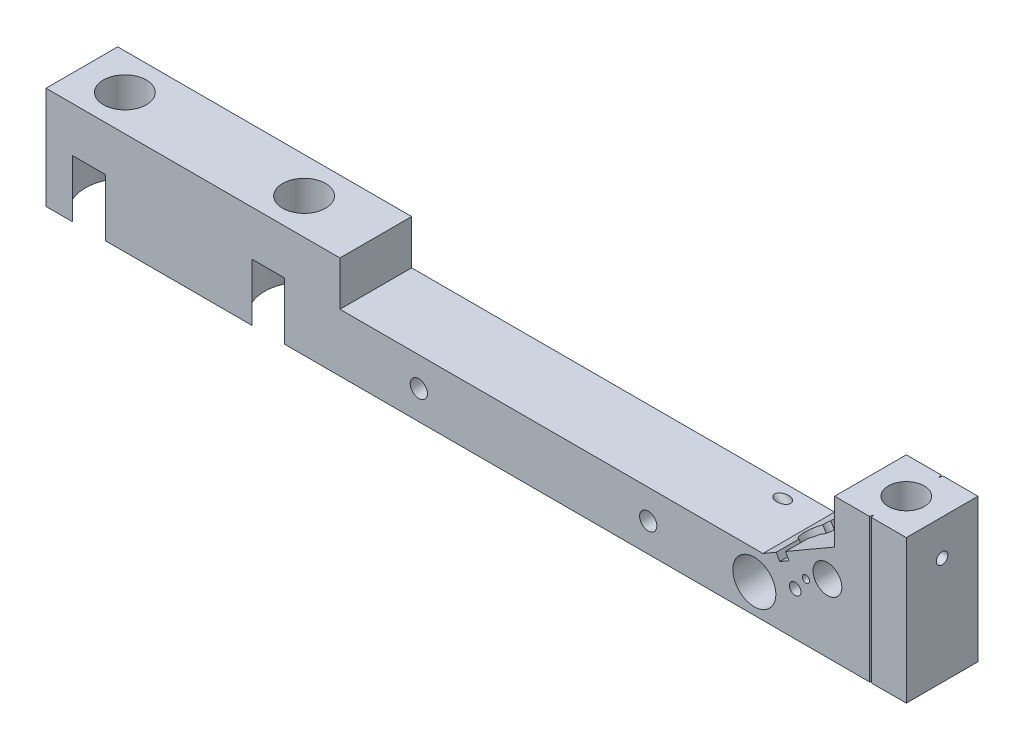
SolidWorks part; units mm, degrees
ref_plane "Front Plane" through (0, 0, 0) normal (0, 0, 1) x (1, 0, 0)
ref_plane "Top Plane" through (0, 0, 0) normal (0, 1, 0) x (1, 0, 0)
ref_plane "Right Plane" through (0, 0, 0) normal (1, 0, 0) x (0, 0, -1)
sketch "Sketch1" plane through (0, 0, 0) normal (0, 1, 0) x (1, 0, 0)
  line L1 (-13.6389, 9.0278) -> (6.3611, 9.0278)
  line L2 (-13.6389, 9.0278) -> (-13.6389, -0.9722)
  line L3 (-13.6389, -0.9722) -> (6.3611, -0.9722)
  line L4 (6.3611, 9.0278) -> (6.3611, -0.9722)
  dimension "D1" = 20
  dimension "D2" = 10
extrude "Boss-Extrude1" add sketch "Sketch1" along normal blind 20
sketch "Sketch2" plane through (0, 20, 0) normal (0, 1, 0) x (1, 0, 0)
  line L0 (-13.6389, 4.0278) -> (6.3611, 4.0278) construction
  line L1 (-13.6389, 9.0278) -> (-13.6389, -0.9722) construction
  line L2 (6.3611, -0.9722) -> (6.3611, 9.0278) construction
  line L3 (1.4951, -0.9722) -> (1.3611, -0.4722)
  line L4 (-13.6389, -0.9722) -> (6.3611, -0.9722) construction
  line L5 (1.3611, -0.4722) -> (1.2271, -0.9722)
  line L6 (1.4951, -0.9722) -> (1.2271, -0.9722)
  line L7 (1.3611, 8.5278) -> (1.2271, 9.0278)
  line L8 (1.4951, 9.0278) -> (1.3611, 8.5278)
  line L9 (1.4951, 9.0278) -> (1.2271, 9.0278)
  circle A0 centre (1.3611, 4.0278) radius 2.5
  dimension "D1" = 5
  dimension "D2" = 5
  dimension "D3" = 30
  dimension "D4" = 0.5
extrude "Cut-Extrude1" cut sketch "Sketch2" against normal through all
sketch "Sketch3" plane through (0, 0, 0.9722) normal (0, 0, 1) x (1, 0, 0)
  line L0 (-13.6389, 20) -> (-3.6389, 20)
  line L1 (-13.6389, 20) -> (1.2271, 20) construction
  line L2 (-3.6389, 13.8564) -> (-10.4894, 9.9013)
  line L3 (-13.6389, 20) -> (-13.6389, 0) construction
  line L4 (-13.6389, 8.0829) -> (-13.6389, 20)
  line L5 (-3.6389, 13.8564) -> (-3.6389, 20)
  line L6 (-13.6389, 0) -> (1.2271, 0) construction
  line L7 (-11.1389, 9.5263) -> (-5.6389, 0) construction
  line L8 (6.3611, 20) -> (6.3611, 0) construction
  line L10 (-10.4894, 9.9013) -> (-9.9894, 9.0353)
  line L11 (-11.7884, 9.1513) -> (-11.2884, 8.2853)
  line L12 (-9.9894, 9.0353) -> (-11.2884, 8.2853)
  line L13 (-11.7884, 9.1513) -> (-13.6389, 8.0829)
  point P1 (-10.6389, 8.6603)
  point P17 (-8.3889, 4.7631)
  dimension "D1" = 30
  dimension "D2" = 11
  dimension "D3" = 12
  dimension "D4" = 10
  dimension "D5" = 1.5
  dimension "D6" = 1
extrude "Cut-Extrude2" cut sketch "Sketch3" against normal through all
sketch "Sketch5" plane through (-6.9097, 11.968, 0) normal (-0.5, 0.866, 0) x (0.866, 0.5, 0)
  line L0 (-4.1334, 9.0278) -> (-4.1334, -0.9722) construction
  line L1 (-4.1334, 4.0278) -> (-5.6334, 4.0278) construction
  line L2 (-5.6334, 9.0278) -> (-5.6334, -0.9722) construction
  arc A0 (-5.85, 5.7214) -> (-3.1898, 3.0612) centre (-4.8834, 4.0278) ccw
  arc A1 (-3.9169, 5.7214) -> (-5.85, 5.7214) centre (-4.8834, 5.9778) ccw
  arc A2 (-3.1898, 3.0612) -> (-3.1898, 4.9943) centre (-2.9334, 4.0278) ccw
  arc A3 (-3.1898, 4.9943) -> (-3.9169, 5.7214) centre (-4.8834, 4.0278) ccw
  point P5 (-4.1334, 4.0278)
  dimension "D1" = 3.9
  dimension "D2" = 2
  dimension "D3" = 2
extrude "Cut-Extrude5" cut sketch "Sketch5" against normal through all
sketch "Sketch6" plane through (6.3611, 0, 0) normal (1, 0, 0) x (0, 0, -1)
  line L1 (-0.9722, 20) -> (9.0278, 20) construction
  point P0 (4.0278, 15)
  point P8 (4.0278, 20)
  dimension "D1" = 5
hole_wizard "M2x0.4 Tapped Hole1" positions "Sketch7" profile "Sketch8" tap size "M2x0.4" standard "BSI"
sketch "Sketch7" plane through (6.3611, 0, 0) normal (1, 0, 0) x (0, 0, -1)
  point P0 (4.0278, 15)
sketch "Sketch8" plane through (6.3611, 15, -4.0278) normal (0, 1, 0) x (0, 0, -1)
  line L0 (0, 0) -> (0, 6.4807)
  line L1 (0, 6.4807) -> (0.8, 6)
  line L2 (0.8, 6) -> (0.8, 0)
  line L5 (0.8, 0) -> (0, 0)
  line L10 (0, 6.4807) -> (-0.8, 6) construction
  line L11 (0, -6.35) -> (0, 107.95) construction
  dimension "Tap Drill Dia." = 1.6
  dimension "Tap Drill Depth" = 6
  dimension "Drill Angle" = 118
cosmetic thread "Hole Thread1" parameters "D1"=4, "D2"=2
hole_wizard "M2x0.4 Tapped Hole2" positions "Sketch9" profile "Sketch10" tap size "M2x0.4" standard "BSI"
sketch "Sketch9" plane through (0, 0, 0.9722) normal (0, 0, 1) x (1, 0, 0)
  line L0 (-11.2884, 8.2853) -> (-9.9894, 9.0353) construction
  line L1 (-9.1389, 6.0622) -> (-10.6389, 8.6603) construction
  point P0 (-9.1389, 6.0622)
  dimension "D1" = 3
sketch "Sketch10" plane through (-9.1389, 6.0622, 0.9722) normal (1, 0, 0) x (0, -1, 0)
  line L0 (0, 0) -> (0, 6.4807)
  line L1 (0, 6.4807) -> (0.8, 6)
  line L2 (0.8, 6) -> (0.8, 0)
  line L5 (0.8, 0) -> (0, 0)
  line L10 (0, 6.4807) -> (-0.8, 6) construction
  line L11 (0, -6.35) -> (0, 107.95) construction
  dimension "Tap Drill Dia." = 1.6
  dimension "Tap Drill Depth" = 6
  dimension "Drill Angle" = 118
cosmetic thread "Hole Thread2" parameters "D1"=4, "D2"=2
sketch "Sketch14" plane through (-13.6389, 0, 0) normal (-1, 0, 0) x (0, 0, 1)
  line L4 (0.9722, 0) -> (0.9722, 8.0829)
  line L5 (0.9722, 8.0829) -> (-9.0278, 8.0829)
  line L6 (-9.0278, 8.0829) -> (-9.0278, 0)
  line L7 (-9.0278, 0) -> (0.9722, 0)
  line L8 (0.9722, 0) -> (0.9722, 8.0829)
  line L9 (0.9722, 8.0829) -> (-9.0278, 8.0829)
  line L10 (-9.0278, 8.0829) -> (-9.0278, 0)
  line L11 (-9.0278, 0) -> (0.9722, 0)
  dimension "D1" = 0
extrude "Boss-Extrude3" add sketch "Sketch14" along normal blind 100
sketch "Sketch15" plane through (0, 8.0829, 0) normal (0, 1, 0) x (1, 0, 0)
  line L1 (-113.6389, -0.9722) -> (-113.6389, 9.0278) construction
  circle A2 centre (-107.6389, 4.0278) radius 3
  circle A3 centre (-82.6389, 4.0278) radius 3
  point P8 (-113.6389, 4.0278)
  dimension "D1" = 6
  dimension "D2" = 6
  dimension "D4" = 6
  dimension "D3" = 25
extrude "Cut-Extrude7" cut sketch "Sketch15" against normal up to next
sketch "Sketch16" plane through (0, 0, 0.9722) normal (0, 0, 1) x (1, 0, 0)
  line L0 (-113.6389, 0) -> (1.2271, 0) construction
  line L3 (-13.6389, 0) -> (-13.6389, 8.0829) construction
  circle A0 centre (-61.6389, 4) radius 1
  circle A1 centre (-29.6389, 4) radius 1
  dimension "D1" = 2
  dimension "D2" = 2
  dimension "D5" = 16
  dimension "D4" = 32
  dimension "D3" = 4
sketch "Sketch18" plane through (0, 0, 0.9722) normal (0, 0, 1) x (1, 0, 0)
  line L0 (-113.6389, 0) -> (1.2271, 0) construction
  line L1 (-13.6389, 0) -> (-13.6389, 8.0829) construction
  circle A0 centre (-7.6389, 8) radius 0.5
  dimension "D1" = 1
  dimension "D2" = 8
  dimension "D3" = 6
extrude "Cut-Extrude9" cut sketch "Sketch18" against normal blind 3
sketch "Sketch23" plane through (0, 0, 0) normal (0, -1, 0) x (1, 0, 0)
  circle A0 centre (-107.6389, -4.0278) radius 5.5
  circle A1 centre (-82.6389, -4.0278) radius 5.5
  dimension "D1" = 11
  dimension "D2" = 11
extrude "Cut-Extrude10" cut sketch "Sketch23" against normal blind 8
sketch "Sketch24" plane through (0, 8.0829, 0) normal (0, 1, 0) x (1, 0, 0)
  line L0 (-113.6389, -0.9722) -> (-13.6389, -0.9722) construction
  line L1 (-72.6389, -0.9722) -> (-113.6389, -0.9722)
  line L2 (-72.6389, -0.9722) -> (-72.6389, 9.0278)
  line L3 (-72.6389, 9.0278) -> (-113.6389, 9.0278)
  line L4 (-113.6389, -0.9722) -> (-113.6389, 9.0278)
  circle A0 centre (-82.6389, 4.0278) radius 3 construction
  circle A1 centre (-107.6389, 4.0278) radius 3
  circle A2 centre (-82.6389, 4.0278) radius 3
  point P9 (-72.6389, 4.0278)
  dimension "D1" = 10
extrude "Boss-Extrude4" add sketch "Sketch24" along normal blind 6.2
sketch "Sketch27" plane through (0, 0, -9.0278) normal (0, 0, -1) x (-1, 0, 0)
  line L0 (-6.3611, 20) -> (-6.3611, 0) construction
  line L1 (-1.2271, 0) -> (80.3476, 0) construction
  circle A0 centre (4.6389, 9.5) radius 2
  dimension "D1" = 4
  dimension "D2" = 11
  dimension "D3" = 9.5
extrude "Cut-Extrude11" cut sketch "Sketch27" against normal through all
ref_axis "Axis1" through (-4.6389, 9.5, 0.9722) along (0, 0, -1)
ref_plane "Plane1" through (0.6345, 0.3663, 0) normal (0.866, 0.5, 0) x (0, 0, -1)
sketch "Sketch28" plane through (-6.9097, 11.968, 0) normal (-0.5, 0.866, 0) x (0.866, 0.5, 0)
  line L0 (3.7768, 4.0278) -> (-99.5675, 4.0278) construction
  line L1 (3.7768, 9.0278) -> (3.7768, -0.9722) construction
  line L2 (0.7326, -4.461) -> (0.7326, 4.461) construction
  point P5 (3.7768, 4.0278)
  point P6 (0.7326, 4.0278)
hole_wizard "M2x0.4 Tapped Hole4" positions "Sketch29" profile "Sketch31" tap size "M2x0.4" standard "BSI" end condition up to next
sketch "Sketch29" plane through (-6.9097, 11.968, 0) normal (-0.5, 0.866, 0) x (0.866, 0.5, 0)
  point P0 (0.7326, 4.0278)
sketch "Sketch31" plane through (-6.2753, 12.3343, -4.0278) normal (0, 0, 1) x (-0.866, -0.5, 0)
  line L0 (0, 0) -> (0, 1.2728)
  line L1 (0, 1.2728) -> (0.8, 1.2728)
  line L2 (0.8, 1.2728) -> (0.8, 0)
  line L5 (0.8, 0) -> (0, 0)
  line L11 (0, -6.35) -> (0, 107.95) construction
  dimension "Thru Tap Drill Dia." = 1.6
  dimension "Thru Tap Drill Depth" = 1.2728
cosmetic thread "Hole Thread5" parameters "D2"=2
sketch "Sketch32" plane through (0, 0, -9.0278) normal (0, 0, -1) x (-1, 0, 0)
  line L0 (13.6389, 8.0829) -> (13.6389, 0) construction
  line L1 (7.8906, 0) -> (12.8276, 8.5513) construction
  circle A0 centre (14.8427, 4.0415) radius 3
  point P5 (13.6389, 4.0415)
  dimension "D1" = 6
  dimension "D2" = 4
extrude "Cut-Extrude12" cut sketch "Sketch32" against normal through all
ref_axis "Axis2" through (-14.8427, 4.0415, 0.9722) along (0, 0, -1)
ref_plane "Plane2" through (-14.8427, 0, 0) normal (1, 0, 0) x (0, 0, -1)
sketch "Sketch33" plane through (0, 8.0829, 0) normal (0, 1, 0) x (1, 0, 0)
  line L2 (-14.8427, -5.5) -> (-14.8427, 5.5) construction
  line L3 (-72.6389, 9.0278) -> (-13.6389, 9.0278) construction
  point P0 (-14.8427, 7.5278)
  dimension "D1" = 1.5
ref_axis "Axis3" through (-61.6389, 4, 0.9722) along (0, 0, -1)
ref_axis "Axis4" through (-29.6389, 4, 0.9722) along (0, 0, -1)
hole_wizard "CBORE for M2 Hex Socket Head Cap2" positions "Sketch40" profile "Sketch41" counterbore size "M2" standard "BSI" end condition through all
sketch "Sketch40" plane through (0, 0, -9.0278) normal (0, 0, -1) x (-1, 0, 0)
  point P0 (61.6389, 4)
  point P3 (29.6389, 4)
sketch "Sketch41" plane through (-61.6389, 4, -9.0278) normal (1, 0, 0) x (0, 1, 0)
  line L0 (0, 0) -> (0, 10)
  line L1 (0, 10) -> (1.2, 10)
  line L3 (1.2, 10) -> (1.2, 2)
  line L4 (1.2, 2) -> (2.2, 2)
  line L5 (2.2, 2) -> (2.2, 0)
  line L7 (2.2, 0) -> (0, 0)
  line L11 (0, -6.35) -> (0, 107.95) construction
  dimension "Thru Hole Dia." = 2.4
  dimension "Thru Hole Depth" = 10
  dimension "C'Bore Dia." = 4.4
  dimension "C'Bore Depth" = 2
ref_plane "Plane3" through (-5.4006, -5.4006, 0) normal (0.7071, 0.7071, 0) x (0, 0, -1)
ref_axis "Axis5" through (-18.8841, 8.0829, -9.5278) along (0, 0, 1)
ref_plane "Plane4" through (-13.4835, 13.4835, 0) normal (-0.7071, 0.7071, 0) x (0, 0, 1)
ref_plane "Plane5" through (-20.5546, 20.5546, 0) normal (-0.7071, 0.7071, 0) x (0, 0, 1)
hole_wizard "M2x0.4 Tapped Hole7" positions "Sketch45" profile "Sketch46" tap size "M2x0.4" standard "BSI" end condition up to next
sketch "Sketch45" plane through (-20.5546, 20.5546, 0) normal (-0.7071, 0.7071, 0) x (0, 0, 1)
  line L0 (-9.5278, -7.6376) -> (1.4722, -7.6376) construction
  line L1 (-9.0278, -45.648) -> (-9.0278, -3.9287) construction
  point P0 (-7.0278, -7.6376)
  dimension "D1" = 2
sketch "Sketch46" plane through (-25.9552, 15.154, -7.0278) normal (0, 0, 1) x (-0.7071, -0.7071, 0)
  line L0 (0, 0) -> (0, 12.7155)
  line L1 (0, 12.7155) -> (0.8, 12.7155)
  line L2 (0.8, 12.7155) -> (0.8, 0)
  line L5 (0.8, 0) -> (0, 0)
  line L11 (0, -6.35) -> (0, 107.95) construction
  dimension "Thru Tap Drill Dia." = 1.6
  dimension "Thru Tap Drill Depth" = 12.7155
cosmetic thread "Hole Thread9" parameters "D2"=2
sketch "Sketch47" [suppressed] plane through (0, 0, -9.0278) normal (0, 0, -1) x (-1, 0, 0)
  line L1 (113.6389, 9.2829) -> (72.6389, 9.2829)
  line L2 (113.6389, 9.2829) -> (113.6389, 0)
  line L3 (113.6389, 0) -> (-6.3611, 0)
  line L4 (-6.3611, 8.0829) -> (-6.3611, 0)
  line L6 (113.6389, 14.2829) -> (113.6389, 0) construction
  line L7 (-6.3611, 20) -> (-6.3611, 0) construction
  line L9 (-6.3611, 20) -> (72.6389, 20)
  line L10 (-6.3611, 20) -> (-6.3611, 8.0829)
  line L12 (72.6389, 20) -> (72.6389, 9.2829)
  line L13 (72.6389, 14.2829) -> (113.6389, 14.2829) construction
  dimension "D1" = 5
extrude "Cut-Extrude13" [suppressed] cut sketch "Sketch47" against normal through all
